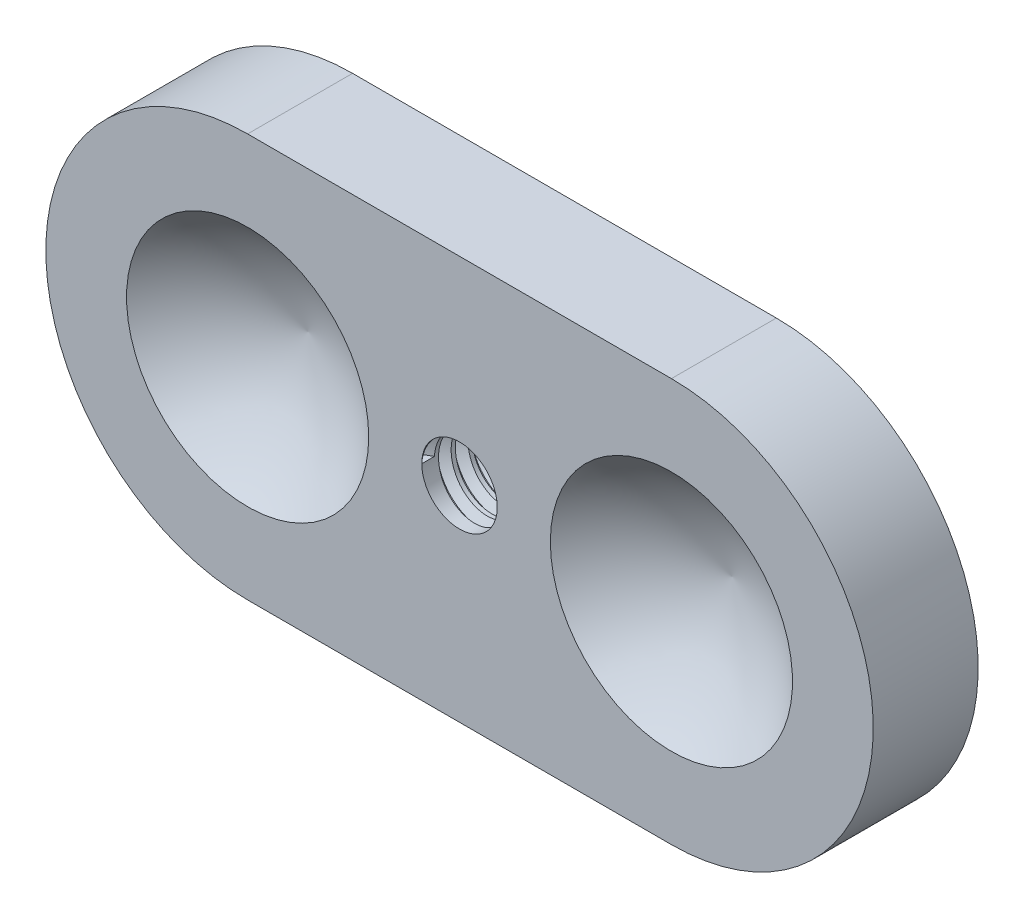
SolidWorks part; units mm, degrees
material "Plain Carbon Steel"
ref_plane "Front Plane" through (0, 0, 0) normal (0, 0, 1) x (1, 0, 0)
ref_plane "Top Plane" through (0, 0, 0) normal (0, 1, 0) x (1, 0, 0)
ref_plane "Right Plane" through (0, 0, 0) normal (1, 0, 0) x (0, 0, -1)
sketch "Sketch1" plane through (0, 0, 0) normal (0, 0, 1) x (1, 0, 0)
  line L0 (-6.6675, 6.2463) -> (6.6675, 6.2463)
  line L1 (-6.6675, -6.4537) -> (6.6675, -6.4537)
  arc A0 (-6.6675, 6.2463) -> (-6.6675, -6.4537) centre (-6.6675, -0.1037) ccw
  arc A1 (6.6675, -6.4537) -> (6.6675, 6.2463) centre (6.6675, -0.1037) ccw
  point P1 (0, 6.2463)
  dimension "D1" = 12.7
extrude "Boss-Extrude1" add sketch "Sketch1" along normal blind 3.302
sketch "Sketch2" plane through (0, 0, 3.302) normal (0, 0, 1) x (1, 0, 0)
  line L0 (0, 0) -> (0, 3.0055)
  circle A0 centre (-6.6675, -0.1037) radius 3.81
  circle A1 centre (6.6675, -0.1037) radius 3.81
  dimension "D1" = 7.62
ref_plane "Plane1" through (6.6675, 0, 0) normal (1, 0, 0) x (0, 0, -1)
sketch "Sketch4" plane through (6.6675, 0, 0) normal (1, 0, 0) x (0, 0, -1)
  line L0 (-3.302, 3.7063) -> (-3.302, -3.9137) construction
  line L1 (-3.302, 3.7063) -> (-3.302, -3.9137)
  line L2 (-3.302, 3.7063) -> (-3.302, -0.1037)
  line L3 (-1.397, -0.1037) -> (-3.302, -0.1037)
  line L4 (-3.302, -0.1037) -> (-5.1659, -0.1037)
  arc A0 (-3.302, 3.7063) -> (-1.397, -0.1037) centre (-8.0268, -1.0373) cw
  dimension "D1" = 1.905
revolve "Cut-Revolve1" cut sketch "Sketch4" angle 360 about L4 region at (6.6675, 1.3161, 2.572)
mirror "Mirror1" about plane through (0, 0, 0) normal (1, 0, 0) of "Cut-Revolve1"
hole_wizard "#4-48 Tapped Hole3" positions "Sketch8" profile "Sketch9" tap size "#4-48" standard "ANSI Inch" end condition through all
sketch "Sketch8" plane through (0, 0, 3.302) normal (0, 0, 1) x (1, 0, 0)
  point P0 (0, 0)
sketch "Sketch9" plane through (0, 0, 3.302) normal (1, 0, 0) x (0, -1, 0)
  line L0 (0, 0) -> (0, 3.302)
  line L1 (0, 3.302) -> (1.1874, 3.302)
  line L2 (1.1874, 3.302) -> (1.1874, 0)
  line L5 (1.1874, 0) -> (0, 0)
  line L11 (0, -6.35) -> (0, 107.95) construction
  dimension "Thru Tap Drill Dia." = 2.3749
  dimension "Thru Tap Drill Depth" = 3.302
thread "Thread1" pitch 0.5292 method cut profile "Thread Profile1" start angle 0, offset 0, length 0, pitch 0.5292, diameter 2.3749
ref_plane "Plane2" through (-1.1874, 0, 3.302) normal (0, -1, 0) x (-1, 0, 0)
sketch "Thread Profile1" plane through (-1.1874, 0, 3.302) normal (0, -1, 0) x (-1, 0, 0)
  line L0 (0, 0) -> (0, 0.5292) construction
  line L1 (0, 0) -> (0.2864, 0.1654)
  line L2 (0.2864, 0.1654) -> (0.2864, 0.2315)
  line L3 (0.2864, 0.2315) -> (0, 0.3969)
  line L4 (0.2864, 0.1984) -> (0, 0.1984) construction
  line L11 (0, 0) -> (0, 0.3969)
  point P2 (0, 0)
  dimension "Pitch" = 0.5292
  dimension "Profile_Angle" = 60
  dimension "Profile_Land" = 0.0661
  dimension "Profile_Height" = 0.2864
